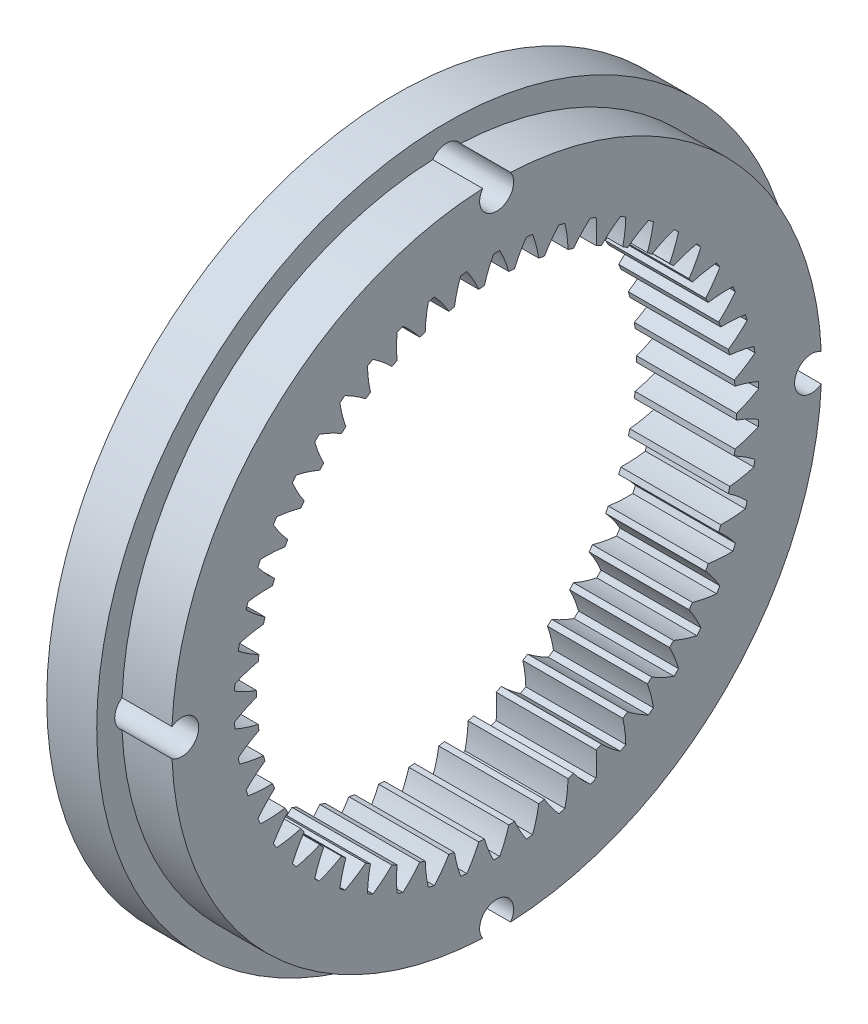
SolidWorks part; units mm, degrees
ref_plane "Plane1" through (0, 0, 0) normal (0, 0, 1) x (1, 0, 0)
ref_plane "Plane2" through (0, 0, 0) normal (0, 1, 0) x (1, 0, 0)
ref_plane "Plane3" through (0, 0, 0) normal (1, 0, 0) x (0, 0, -1)
sketch "HoldingSke" plane through (0, 0, 0) normal (0, 1, 0) x (1, 0, 0)
  line L0 (0, 0) -> (0.6428, -0.766)
  line L1 (-15, 0) -> (100, 0) construction
  line L2 (0, 0) -> (-2.1039, 2.3779)
  line L3 (0, 0) -> (-11.863, 4.5341)
  line L4 (0, 0) -> (5.5511, 6.6156)
  line L5 (0, 0) -> (-23.7986, -8.8762)
  line L6 (0, 0) -> (-10.5278, -7.1032)
  line L7 (-2.1039, 2.3779) -> (3.3635, 27.1825)
  line L8 (-76.2, 3.3779) -> (-54.61, 3.3779)
  line L9 (-71.009, 38.7566) -> (-53.1078, 45.2721)
  line L10 (-76.2, 71.12) -> (104.1128, 71.12)
  line L11 (0, 0) -> (-10, 0)
  line L12 (-76.2, 101.6) -> (-76.162, 101.6)
  line L13 (24.9733, 27.94) -> (52.9518, 28.4284)
  line L14 (24.9733, 27.94) -> (24.9743, 27.94)
  line L15 (24.9733, 27.94) -> (100.4006, 29.5858)
  circle A0 centre (0, 0) radius 35
  circle A1 centre (0, 0) radius 12.7
  circle A2 centre (0, 0) radius 12.7
  dimension "Num_teeth" = 50
  dimension "Pitch_radius" = 180.3128
  dimension "Width" = 10
  dimension "Diameter" = 70
sketch "BasProSke" plane through (0, 0, 0) normal (0, 1, 0) x (1, 0, 0)
  line L0 (-10, 0) -> (60, 0) construction
  line L1 (0, 24) -> (0, 35)
  line L2 (0, 24) -> (10, 24)
  line L3 (10, 24) -> (10, 35)
  line L4 (10, 35) -> (0, 35)
  dimension "Thickness" = 10
  dimension "Diameter" = 70
revolve "Base-Revolve" add sketch "BasProSke" angle 360 about L0
sketch "TooCutSke" plane through (0, 0, 0) normal (1, 0, 0) x (0, 0, -1)
  line L3 (0.8803, 24.9845) -> (0.8803, 53.6633) construction
  line L4 (0, 0) -> (0, 59.563) construction
  line L5 (0, 0) -> (-4.2903, 68.1927) construction
  line L6 (-10.7899, 20.506) -> (36.4405, 23.4775) construction
  circle A0 centre (0, 0) radius 25 construction
  circle A1 centre (0, 0) radius 26.251 construction
  circle A2 centre (0, 0) radius 21.1431 construction
  circle A3 centre (0, 0) radius 23.9746 construction
  arc A4 (1.2282, 23.9431) -> (0.3126, 26.2491) centre (-10.7899, 20.506) ccw
  arc A5 (1.2282, 23.9431) -> (-1.2282, 23.9431) centre (0, 0) ccw
  arc A6 (0.3126, 26.2491) -> (-0.3126, 26.2491) centre (0, 0) ccw
  arc A7 (-0.3126, 26.2491) -> (-1.2282, 23.9431) centre (10.7899, 20.506) ccw
extrude "ToothCut" cut sketch "TooCutSke" along normal through all
fillet "Breaks" [suppressed] radius 0.1
fillet "RootFillets" [suppressed] radius 0.251
pattern_circular "TeethCuts" count 50 every 7.2 about axis through (-10, 0, 0) along (1, 0, 0) of "RootFillets", "Breaks", "ToothCut"
sketch "Croquis2" plane through (0, 0, 0) normal (-1, 0, 0) x (0, 0, 1)
  circle A0 centre (0, 0) radius 25 construction
  circle A1 centre (31.5, 0) radius 1.7
  circle A2 centre (0, 0) radius 31.5 construction
  circle A3 centre (0, 31.5) radius 1.7
  circle A6 centre (0, -31.5) radius 1.7
  circle A7 centre (-31.5, 0) radius 1.7
  point P13 (0, 0)
  point P16 (0, 0)
  dimension "D1" = 50
  dimension "D2" = 63
  dimension "D3" = 3.4
  dimension "D4" = 4
extrude "Cortar-Extruir1" cut sketch "Croquis2" against normal up to surface (10 mm away) up to face at (10, 0, 35)
sketch "Croquis3" plane through (10, 0, 0) normal (1, 0, 0) x (0, 0, -1)
  circle A0 centre (0, 0) radius 32.5
  circle A1 centre (0, 0) radius 35
  dimension "D1" = 65
extrude "Cortar-Extruir2" cut sketch "Croquis3" against normal blind 5
equation "' \"Module@HoldingSke\" = 6.35"
equation "' \"Num_teeth@HoldingSke\" = 24"
equation "' \"Ap@HoldingSke\" =  14.5"
equation "' \"Ap@HoldingSke\" = 14.5"
equation "' \"Width@HoldingSke\" = 12"
equation "' \"Diameter@HoldingSke\" = 8 * 25.4"
equation "' \"Show_teeth@HoldingSke\" = 100"
equation "' \"Backlash@HoldingSke\" = 0.009 * 25.4"
equation "' \"Addendum_fac@HoldingSke\" = 1.0"
equation "' \"Dedendum_fac@HoldingSke\" = 1.25"
equation "' \"Dedendum_add@HoldingSke\" = 0.00005 * 25.4"
equation "' \"Clearance_fac@HoldingSke\" = 0.25"
equation "\"Pitch@HoldingSke\" = 1 / \"Module@HoldingSke\" "
equation "\"Overcut_dia@TooCutSke\" = (\"Num_teeth@HoldingSke\" - 2 * \"Addendum_fac@HoldingSke\") / \"Pitch@HoldingSke\" - 0.002 * 25.4"
equation "\"Pitch_dia@TooCutSke\" = \"Num_teeth@HoldingSke\" / \"Pitch@HoldingSke\""
equation "\"Base_dia@TooCutSke\" = \"Num_teeth@HoldingSke\" / \"Pitch@HoldingSke\" * cos((\"Ap@HoldingSke\"  * 3.14159265 / 180)) * 0.90"
equation "\"Root_dia@TooCutSke\" = \"Num_teeth@HoldingSke\"  / \"Pitch@HoldingSke\" + 2 *  \"Dedendum_fac@HoldingSke\"/ \"Pitch@HoldingSke\" + \"Dedendum_add@HoldingSke\" * 2"
equation "\"Half_ang@TooCutSke\" = 180 / \"Num_teeth@HoldingSke\""
equation "\"Half_CT@TooCutSke\" = \"Num_teeth@HoldingSke\" / \"Pitch@HoldingSke\" * sin((3.14159265 / 2 / \"Num_teeth@HoldingSke\")) / 2 + 10 * \"Backlash@HoldingSke\" / 4"
equation "\"Flank_rad@TooCutSke\" = \"Num_teeth@HoldingSke\" / \"Pitch@HoldingSke\" / 4"
equation "\"Radius@RootFillets\"= \"Clearance_fac@HoldingSke\" / \"Pitch@HoldingSke\" + \"Dedendum_add@HoldingSke\""
equation "\"Break_rad@Breaks\" = 0.02 / \"Pitch@HoldingSke\" * 5"
equation "\"Num_teeth@TeethCuts\" = int( \"Show_teeth@HoldingSke\" ) + 1"
equation "\"Num_teeth@TeethCuts\" = ((sgn( \"Num_teeth@TeethCuts\" - \"Num_teeth@HoldingSke\" )-1)*( \"Num_teeth@TeethCuts\" - \"Num_teeth@HoldingSke\" ))/-2+ \"Num_teeth@HoldingSke\""
equation "\"Num_teeth@TeethCuts\" = ((sgn( \"Num_teeth@TeethCuts\" - 2.0)+1)*( \"Num_teeth@TeethCuts\" - 2.0))/2 +2.0"
equation "\"Angle@TeethCuts\" = 360.0 / \"Num_teeth@HoldingSke\""
equation "\"Diameter@BasProSke\" = \"Num_teeth@HoldingSke\"  / \"Pitch@HoldingSke\" + 2 *  \"Dedendum_fac@HoldingSke\"/ \"Pitch@HoldingSke\" + \"Dedendum_add@HoldingSke\" * 2 + 0.002 * 25.4"
equation "\"Diameter@BasProSke\" = ((sgn( \"Diameter@BasProSke\"  - \"Diameter@HoldingSke\" )+1)*( \"Diameter@BasProSke\"  - \"Diameter@HoldingSke\" ))/2 + \"Diameter@HoldingSke\""
equation "\"Inside_diameter@BasProSke\" =  (\"Num_teeth@HoldingSke\" - 2 * \"Addendum_fac@HoldingSke\") / \"Pitch@HoldingSke\" "
equation "\"Thickness@BasProSke\"  = \"Width@HoldingSke\""
